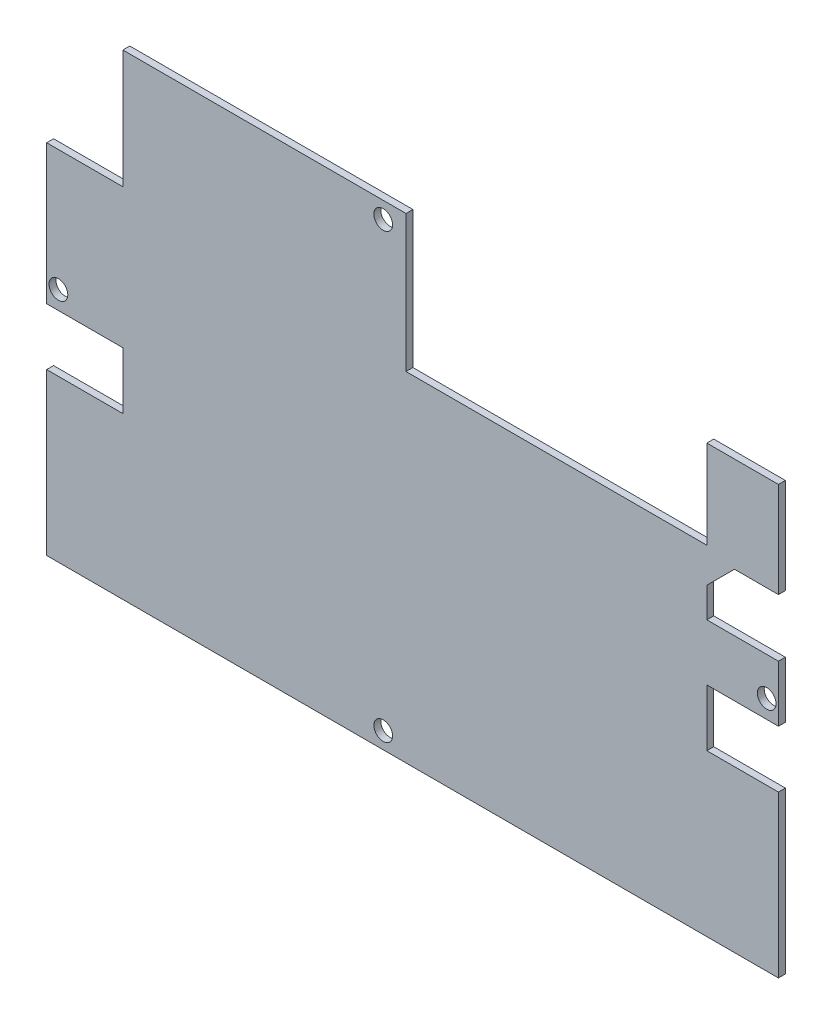
SolidWorks part; units mm, degrees
ref_plane "Front Plane" through (0, 0, 0) normal (0, 0, 1) x (1, 0, 0)
ref_plane "Top Plane" through (0, 0, 0) normal (0, 1, 0) x (1, 0, 0)
ref_plane "Right Plane" through (0, 0, 0) normal (1, 0, 0) x (0, 0, -1)
sketch "Sketch1" plane through (0, 0, 0) normal (0, 0, 1) x (1, 0, 0)
  line L0 (9.878, 12.192) -> (9.878, -93.472) construction
  line L1 (-41.367, 14.097) -> (6.6634, 14.097)
  line L2 (-41.367, 14.097) -> (-41.367, -13.0805)
  line L3 (-38.029, -95.123) -> (9.878, -95.123)
  line L4 (91.388, 14.5) -> (91.388, -20.5) construction
  line L5 (-41.367, 14.097) -> (9.878, -95.123) construction
  line L6 (-38.029, -95.123) -> (6.6634, 14.097) construction
  line L8 (-38.029, -95.123) -> (-58.8607, -95.123)
  line L10 (-41.367, -58.1655) -> (-58.8607, -58.1655)
  line L11 (-58.8607, -95.123) -> (-58.8607, -58.1655)
  line L12 (-38.029, -95.123) -> (-58.8607, -58.1655) construction
  line L13 (-41.367, -58.1655) -> (-58.8607, -95.123) construction
  line L14 (9.878, -95.123) -> (90.0829, -95.123)
  line L15 (99.008, -18.923) -> (109.0968, -18.923)
  line L16 (23.618, -17.32) -> (92.658, -17.32)
  line L17 (92.658, -58.1655) -> (92.658, -45.0855)
  line L18 (9.878, -95.123) -> (92.658, -17.32) construction
  line L19 (7.5194, -20.856) -> (90.0829, -95.123) construction
  line L20 (24.888, -20.5) -> (24.888, 14.5) construction
  line L21 (6.6634, 14.097) -> (23.618, 14.097)
  line L22 (92.658, -17.32) -> (92.658, 2.9845)
  line L23 (92.658, 2.9845) -> (109.0968, 2.9845)
  line L24 (23.618, 14.097) -> (23.618, -17.32)
  line L25 (6.6634, 14.097) -> (23.618, -17.32) construction
  line L26 (6.8209, -14.9887) -> (23.618, 14.097) construction
  line L27 (109.0968, -18.923) -> (109.0968, 2.9845)
  line L28 (90.0829, -95.123) -> (109.0968, -95.123)
  line L29 (92.658, -10.8044) -> (109.0968, 2.9845) construction
  line L30 (92.658, -58.1655) -> (109.0968, -58.1655)
  line L31 (109.0968, -95.123) -> (109.0968, -58.1655)
  line L32 (90.0829, -95.123) -> (109.0968, -58.1655) construction
  line L33 (92.658, -58.1655) -> (109.0968, -95.123) construction
  line L34 (92.658, 2.9845) -> (109.0968, -18.923) construction
  line L35 (99.008, -18.923) -> (92.658, -25.273)
  line L36 (89.888, -16.05) -> (26.388, -16.05) construction
  line L38 (-58.8607, -13.0805) -> (-41.367, -13.0805)
  line L39 (-58.8607, -13.0805) -> (-58.8607, -45.0855)
  line L40 (-58.8607, -45.0855) -> (-41.367, -45.0855)
  line L42 (-58.8607, -13.0805) -> (-41.367, -45.0855) construction
  line L43 (-58.8607, -45.0855) -> (-41.367, -13.0805) construction
  line L44 (-41.367, -45.0855) -> (-41.367, -58.1655)
  line L45 (111.6368, -97.663) -> (-61.4007, -97.663) construction
  line L46 (-44.732, 16.637) -> (94.968, 16.637) construction
  line L47 (-43.907, -8.6021) -> (-43.907, -4.4789) construction
  line L48 (-45.8454, -10.5405) -> (-49.9686, -10.5405) construction
  line L49 (-61.4007, -97.663) -> (-61.4007, 5.5245) construction
  line L50 (-45.8454, -47.6255) -> (-49.9686, -47.6255) construction
  line L51 (-45.8454, -55.6255) -> (-49.9686, -55.6255) construction
  line L52 (100.048, 5.5245) -> (111.6368, 5.5245) construction
  line L53 (111.6368, 5.5245) -> (111.6368, -97.663) construction
  line L54 (101.4746, -55.6255) -> (97.3514, -55.6255) construction
  line L55 (101.4746, -47.6255) -> (97.3514, -47.6255) construction
  line L56 (92.658, -32.1509) -> (109.0968, -32.1509)
  line L58 (92.658, -45.0855) -> (109.0968, -45.0855)
  line L59 (109.0968, -32.1509) -> (109.0968, -45.0855)
  line L60 (92.658, -32.1509) -> (109.0968, -45.0855) construction
  line L61 (92.658, -45.0855) -> (109.0968, -32.1509) construction
  line L62 (92.658, -32.1509) -> (92.658, -25.273)
  point P4 (-15.7115, -40.5833)
  point P12 (-49.352, -75.0348)
  point P17 (49.1005, -58.2587)
  point P26 (14.8536, -1.0794)
  point P32 (100.2804, -75.3021)
  point P38 (99.008, -5.478)
  point P52 (-50.1139, -29.083)
  point P76 (100.8774, -38.6182)
  dimension "D4" = 45
  dimension "D1" = 1.27
  dimension "D2" = 1.27
  dimension "D5" = 1.27
  dimension "D6" = 2.54
  dimension "D7" = 2.54
  dimension "D8" = 2.54
  dimension "D9" = 2.54
  dimension "D10" = 2.54
  dimension "D11" = 2.54
  dimension "D12" = 2.54
  dimension "D13" = 2.54
  dimension "D14" = 2.54
  dimension "D15" = 2.54
  dimension "D17" = 2.54
  dimension "D18" = 2.54
  dimension "D19" = 6.35
extrude "Boss-Extrude1" add sketch "Sketch1" along normal blind 1.5875 contours L1 L21 L24 L16 L22 L23 L27 L15 L35 L62 L56 L59 L58 L17 L30 L31 L28 L14 L3 L8 L11 L10 L44 L40 L39 L38 L2
hole_wizard "#6 Clearance Hole1" positions "Sketch3" profile "Sketch2" hole size "#6" standard "ANSI Inch" end condition through all
sketch "Sketch3" plane through (0, 0, 0) normal (0, 0, -1) x (-1, 0, 0)
  point P0 (-106.398, -40.894)
  point P2 (-18.387, 10.287)
  point P4 (56.162, -40.894)
  point P6 (-18.387, -91.313)
sketch "Sketch2" plane through (106.398, -40.894, 0) normal (1, 0, 0) x (0, 1, 0)
  line L0 (0, 0) -> (0, 1.5875)
  line L1 (0, 1.5875) -> (2.1526, 1.5875)
  line L2 (2.1526, 1.5875) -> (2.1526, 0)
  line L5 (2.1526, 0) -> (0, 0)
  line L11 (0, -6.35) -> (0, 107.95) construction
  dimension "Thru Hole Dia." = 4.3053
  dimension "Thru Hole Depth" = 1.5875
